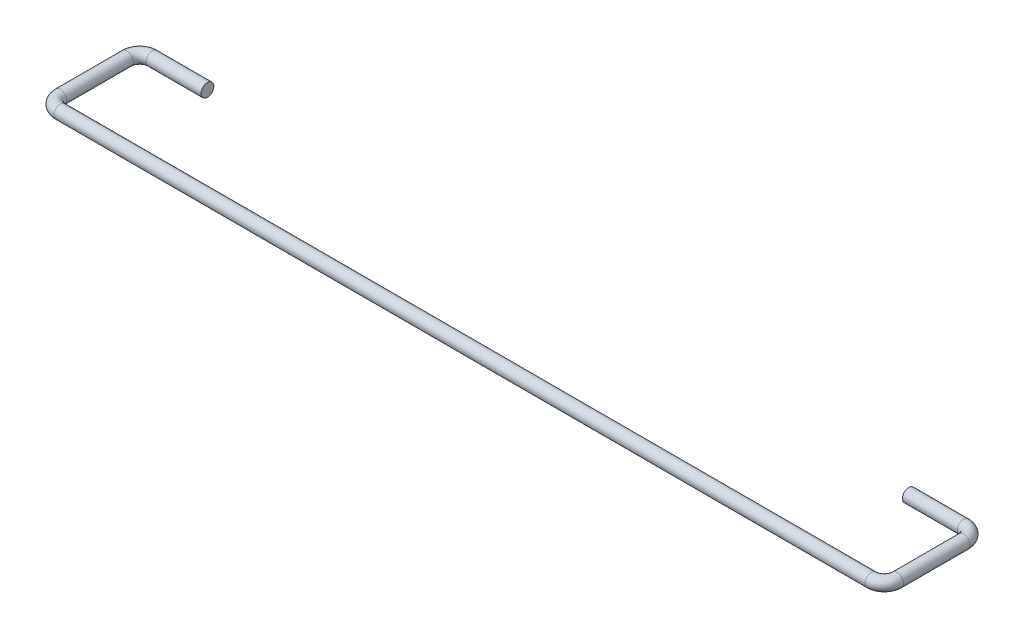
SolidWorks part; units mm, degrees
ref_plane "Front Plane" through (0, 0, 0) normal (0, 0, 1) x (1, 0, 0)
ref_plane "Top Plane" through (0, 0, 0) normal (0, 1, 0) x (1, 0, 0)
ref_plane "Right Plane" through (0, 0, 0) normal (1, 0, 0) x (0, 0, -1)
sketch "Path" plane through (0, 0, 0) normal (0, 1, 0) x (1, 0, 0)
  line L0 (-43.75, -994.1483) -> (-43.75, 49005.8517) construction
  line L1 (-50.6, 11.5) -> (-43.75, 11.5)
  line L2 (-52.2, 9.9) -> (-52.2, 1.6)
  line L3 (-50.6, 0) -> (50.6, 0)
  line L4 (52.2, 9.9) -> (52.2, 1.6)
  line L5 (-52.2, 11.5) -> (52.2, 0) construction
  line L6 (-52.2, 0) -> (52.2, 11.5) construction
  line L7 (43.75, -994.429) -> (43.75, 49005.571) construction
  line L8 (-1000, 5.75) -> (49000, 5.75) construction
  line L9 (0, -995.1) -> (0, 49004.9) construction
  line L10 (43.75, 11.5) -> (50.6, 11.5)
  arc A0 (50.6, 11.5) -> (52.2, 9.9) centre (50.6, 9.9) cw
  arc A1 (50.6, 0) -> (52.2, 1.6) centre (50.6, 1.6) ccw
  arc A2 (-52.2, 1.6) -> (-50.6, 0) centre (-50.6, 1.6) ccw
  arc A3 (-50.6, 11.5) -> (-52.2, 9.9) centre (-50.6, 9.9) ccw
  point P0 (0, 5.75)
  point P11 (-43.75, 5.75)
  point P13 (43.75, 5.75)
  point P14 (0, 0)
  point P16 (0, 0)
  point P32 (0, 0)
  dimension "D4" = 1.6
  dimension "D1" = 11.5
  dimension "D2" = 104.4
  dimension "D3" = 87.5
ref_plane "Plane1" through (-43.75, 0, 0) normal (1, 0, 0) x (0, 0, -1)
sketch "Segment" plane through (-43.75, 0, 0) normal (1, 0, 0) x (0, 0, -1)
  line L0 (-200994.1483, 0) -> (249005.8517, 0) construction
  circle A0 centre (11.5, 0) radius 0.8
  point P4 (0, 0)
  point P5 (0, 0)
  dimension "D1" = 1.6
sweep "Wire" add profiles "Segment" path "Path"
